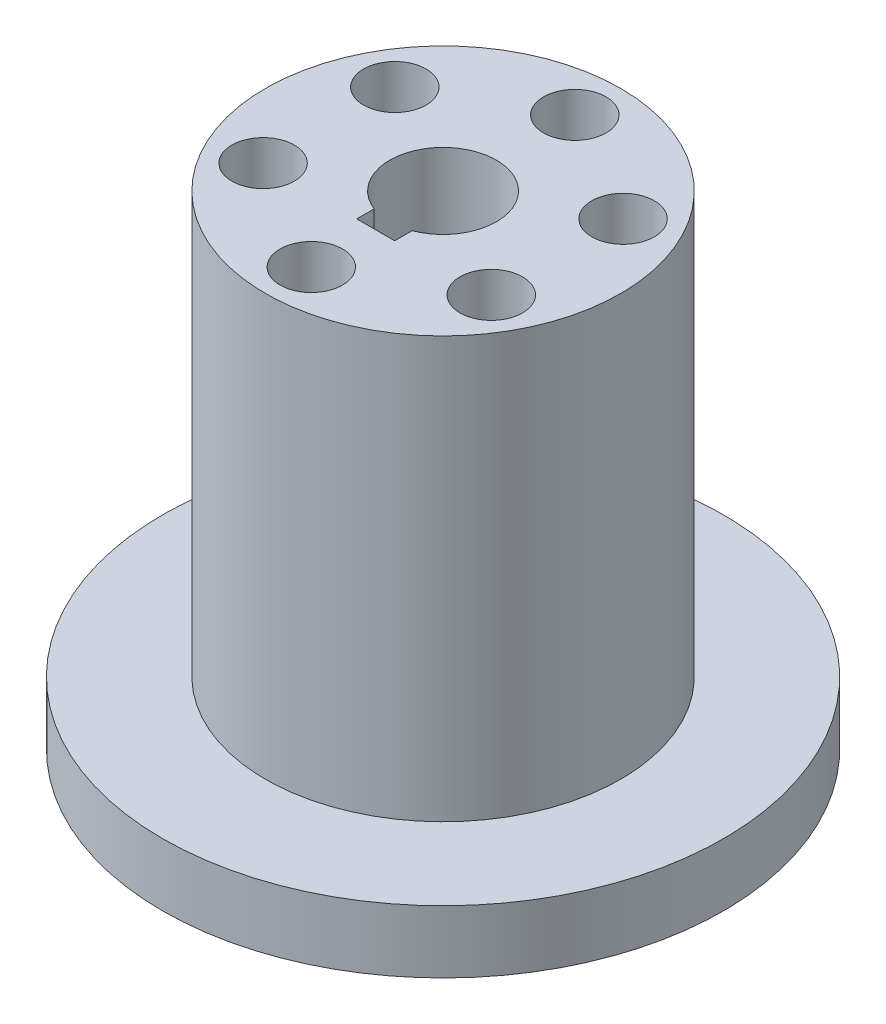
SolidWorks part; units mm, degrees
ref_plane "Front Plane" through (0, 0, 0) normal (0, 0, 1) x (1, 0, 0)
ref_plane "Top Plane" through (0, 0, 0) normal (0, 1, 0) x (1, 0, 0)
ref_plane "Right Plane" through (0, 0, 0) normal (1, 0, 0) x (0, 0, -1)
sketch "Sketch1" plane through (0, 0, 0) normal (0, 1, 0) x (1, 0, 0)
  circle A0 centre (0, 0) radius 38.1
extrude "Boss-Extrude1" add sketch "Sketch1" along normal blind 8.5
sketch "Sketch2" plane through (0, 8.5, 0) normal (0, 1, 0) x (1, 0, 0)
  circle A0 centre (0, 0) radius 24.13
extrude "Boss-Extrude2" add sketch "Sketch2" along normal blind 57.15
sketch "Sketch3" plane through (0, 65.65, 0) normal (0, 1, 0) x (1, 0, 0)
  line L1 (0, 17.8979) -> (-15.5, 8.9489)
  line L2 (-15.5, 8.9489) -> (-15.5, -8.9489)
  line L3 (-15.5, -8.9489) -> (0, -17.8979)
  line L4 (0, -17.8979) -> (15.5, -8.9489)
  line L5 (15.5, -8.9489) -> (15.5, 8.9489)
  line L6 (15.5, 8.9489) -> (0, 17.8979)
  circle A0 centre (0, 0) radius 15.5 construction
  circle A1 centre (0, 17.8979) radius 4.25
  circle A2 centre (15.5, 8.9489) radius 4.25
  circle A3 centre (15.5, -8.9489) radius 4.25
  circle A4 centre (0, -17.8979) radius 4.25
  circle A5 centre (-15.5, -8.9489) radius 4.25
  circle A6 centre (-15.5, 8.9489) radius 4.25
extrude "Cut-Extrude1" cut sketch "Sketch3" against normal blind 78.54 contours L1 A6 L2 | L6 A1 L1 | L5 A2 L6 | L4 A3 L5 | L3 A4 L4 | L2 A5 L3 | L3 A5 L2 | L2 A6 L1 | L1 A1 L6 | L6 A2 L5 | L5 A3 L4 | L4 A4 L3 region at (0, 65.65, -15.5547) region at (0, 65.65, -19.0694) region at (-13.4708, 65.65, -7.7774) region at (-16.5146, 65.65, -9.5347) region at (16.5146, 65.65, -9.5347) region at (13.4708, 65.65, -7.7774) region at (-13.4708, 65.65, 7.7774) region at (-16.5146, 65.65, 9.5347) region at (16.5146, 65.65, 9.5347) region at (13.4708, 65.65, 7.7774) region at (0, 65.65, 15.5547) region at (0, 65.65, 19.0694)
sketch "Sketch4" plane through (0, 0, 0) normal (0, -1, 0) x (1, 0, 0)
  circle A0 centre (-15.5, 8.9489) radius 6.75
  circle A1 centre (0, 17.8979) radius 6.75
  circle A2 centre (15.5, 8.9489) radius 6.75
  circle A3 centre (15.5, -8.9489) radius 6.75
  circle A4 centre (0, -17.8979) radius 6.75
  circle A5 centre (-15.5, -8.9489) radius 6.75
extrude "Cut-Extrude2" cut sketch "Sketch4" against normal blind 8
sketch "Sketch5" plane through (0, 0, 0) normal (0, -1, 0) x (1, 0, 0)
  line L1 (-2.575, 9.15) -> (2.575, 9.15)
  line L2 (-2.575, 9.15) -> (-2.575, 4)
  line L3 (-2.575, 4) -> (2.575, 4)
  line L4 (2.575, 9.15) -> (2.575, 4)
  circle A0 centre (0, 0) radius 7.25
  dimension "D1" = 5.15
  dimension "D2" = 5.15
  dimension "D3" = 9.15
  dimension "D4" = 2.575
extrude "Cut-Extrude3" cut sketch "Sketch5" against normal blind 91 contours L2 A0 L4 L3 | L4 A0 L2 L3 | A0 L4 L1 L2 region at (0, 0, 8.1175) region at (0, 0, 5.5505) region at (0, 0, -0.5929)
